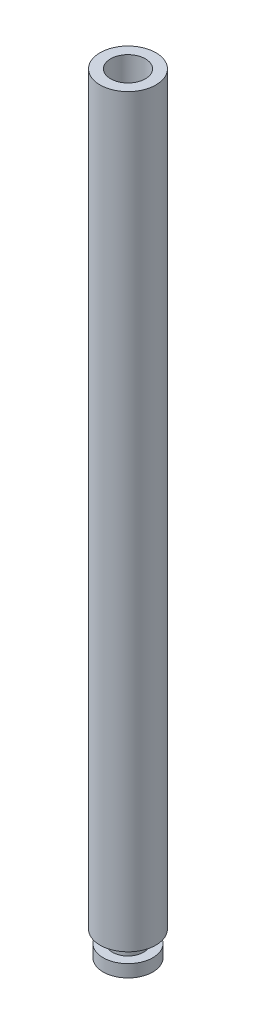
SolidWorks part; units mm, degrees
ref_plane "Front Plane" through (0, 0, 0) normal (0, 0, 1) x (1, 0, 0)
ref_plane "Top Plane" through (0, 0, 0) normal (0, 1, 0) x (1, 0, 0)
ref_plane "Right Plane" through (0, 0, 0) normal (1, 0, 0) x (0, 0, -1)
sketch "Sketch1" plane through (0, 0, 0) normal (0, 1, 0) x (1, 0, 0)
  circle A0 centre (-0.522, 0.5111) radius 1.375
  circle A1 centre (-0.522, 0.5111) radius 2.25
  dimension "D1" = 2.75
  dimension "D2" = 4.5
extrude "Boss-Extrude1" add sketch "Sketch1" along normal blind 60 contours A1
extrude "Boss-Extrude2" add sketch "Sketch1<3>" along normal blind 1 contours A0 region at (-0.522, 0, -0.5111)
sketch "Sketch1<3>" plane through (0, 0, 0) normal (0, 1, 0) x (1, 0, 0) same geometry as "Sketch1"
sketch "Sketch5" plane through (0, 0, 0) normal (0, -1, 0) x (1, 0, 0)
  circle A3 centre (-0.522, -0.5111) radius 1.25
  dimension "D1" = 2.5
extrude "Boss-Extrude3" add sketch "Sketch5" along normal blind 1 contours A3
sketch "Sketch6" plane through (0, -1, 0) normal (0, -1, 0) x (1, 0, 0)
  circle A0 centre (-0.522, -0.5111) radius 2
  dimension "D1" = 4
extrude "Boss-Extrude4" add sketch "Sketch6" along normal blind 1
sketch "Sketch8" plane through (0, -2, 0) normal (0, -1, 0) x (-1, 0, 0)
  circle A0 centre (0.522, 0.5111) radius 1.5
  dimension "D1" = 3
sketch "Sketch11" plane through (0, 60, 0) normal (0, 1, 0) x (1, 0, 0)
  text T0 "VIII" font "Century Gothic" height in points 5
sketch "Sketch12" plane through (0, 60, 0) normal (0, 1, 0) x (1, 0, 0)
  circle A0 centre (-0.522, 0.5111) radius 1.4
  dimension "D1" = 2.8
extrude "Cut-Extrude1" cut sketch "Sketch12" against normal blind 15
